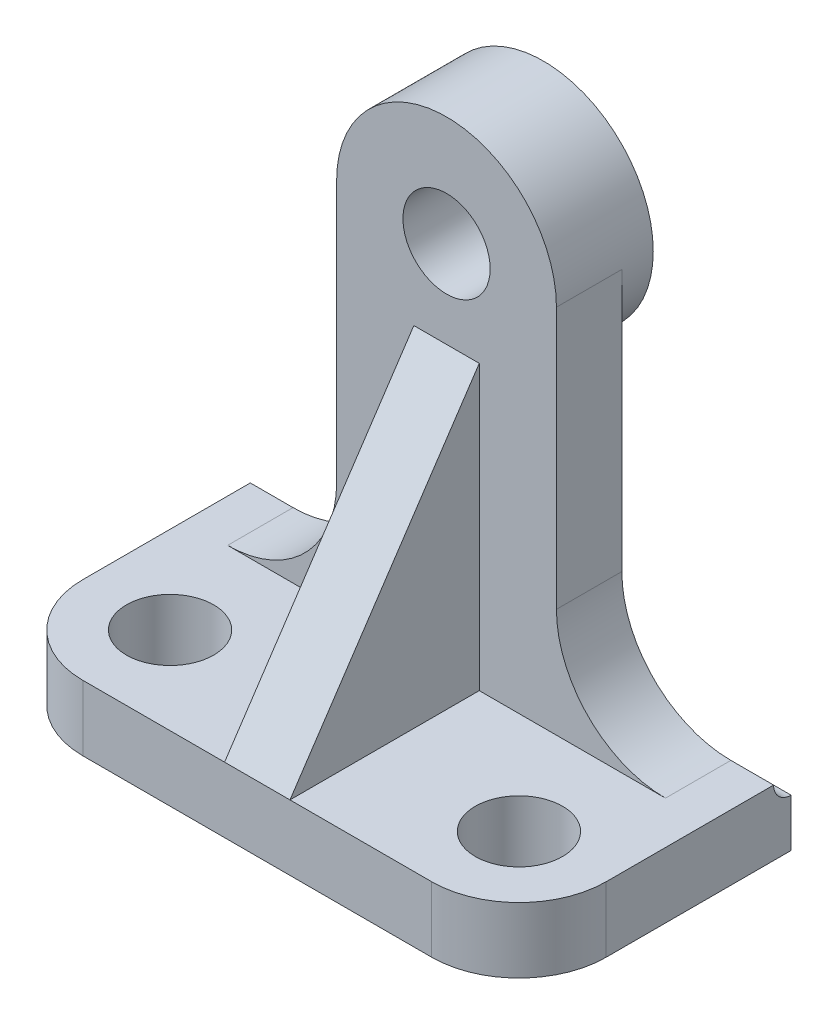
SolidWorks part; units mm, degrees
material "Gray Cast Iron"
ref_plane "Front Plane" through (0, 0, 0) normal (0, 0, 1) x (1, 0, 0)
ref_plane "Top Plane" through (0, 0, 0) normal (0, 1, 0) x (1, 0, 0)
ref_plane "Right Plane" through (0, 0, 0) normal (1, 0, 0) x (0, 0, -1)
ref_axis "X-axis" through (-88.99, 0, 0) along (1, 0, 0)
ref_axis "Y-axis" through (0, 55, 0) along (0, -1, 0)
ref_axis "Z-axis" through (0, 0, -88.99) along (0, 0, 1)
sketch "Sketch1" plane through (0, 0, 0) normal (1, 0, 0) x (0, 0, -1)
  line L0 (0, 0) -> (-37.084, 0)
  line L1 (-37.084, 0) -> (-37.084, -9.525)
  line L2 (-37.084, -9.525) -> (2.54, -9.525)
  line L3 (2.54, -9.525) -> (2.54, -2.54)
  arc A0 (2.54, -2.54) -> (0, 0) centre (2.54, 0) cw
  dimension "D3" = 2.54
  dimension "D1" = 39.624
  dimension "D2" = 9.525
  dimension "D4" = 6.985
extrude "Boss-Extrude1" add sketch "Sketch1" along normal mid plane 76.2
sketch "Sketch2" plane through (0, 0, 0) normal (0, 0, 1) x (1, 0, 0)
  line L0 (-16.002, 0) -> (16.002, 0)
  line L1 (38.1, 0) -> (-38.1, 0) construction
  line L2 (-16.002, 0) -> (-16.002, 53.975)
  line L3 (16.002, 53.975) -> (16.002, 0)
  line L4 (38.1, -9.525) -> (-38.1, -9.525) construction
  arc A0 (-16.002, 53.975) -> (16.002, 53.975) centre (0, 53.975) cw
  dimension "D1" = 16.002
  dimension "D2" = 63.5
extrude "Boss-Extrude2" add sketch "Sketch2" along normal blind 9.525
sketch "Sketch3" plane through (0, 0, 0) normal (0, 0, -1) x (-1, 0, 0)
  circle A0 centre (0, 53.975) radius 16.002
extrude "Boss-Extrude3" add sketch "Sketch3" along normal blind 4.572
sketch "Sketch4" plane through (0, 0, 0) normal (1, 0, 0) x (0, 0, -1)
  line L0 (-9.525, 41.275) -> (-37.084, 0)
  line L1 (-9.525, 0) -> (-9.525, 53.975) construction
  line L2 (-37.084, 0) -> (-9.525, 0)
  line L3 (-9.525, 0) -> (-9.525, 41.275)
  line L4 (-37.084, -9.525) -> (2.54, -9.525) construction
  dimension "D1" = 50.8
extrude "Boss-Extrude4" add sketch "Sketch4" along normal mid plane 9.525
fillet "Fillet1" radius 15.875 2 edges at (-16.002, 0, 4.7625) (16.002, 0, 4.7625)
fillet "Fillet2" radius 12.7 2 edges at (-38.1, -4.7625, 37.084) (38.1, -4.7625, 37.084)
hole_wizard "1/4 (0.5) Diameter Hole1" positions "Sketch6" profile "Sketch7" hole size "1/4" standard "ANSI Inch" end condition through all
sketch "Sketch6" plane through (0, 0, 0) normal (0, 1, 0) x (1, 0, 0)
  point P0 (-25.4, -24.384)
  point P3 (25.4, -24.384)
sketch "Sketch7" plane through (-25.4, 0, 24.384) normal (1, 0, 0) x (0, 0, 1)
  line L0 (0, 0) -> (0, 9.525)
  line L1 (0, 9.525) -> (6.35, 9.525)
  line L2 (6.35, 9.525) -> (6.35, 0)
  line L5 (6.35, 0) -> (0, 0)
  line L11 (0, -6.35) -> (0, 107.95) construction
  dimension "Thru Hole Dia." = 12.7
  dimension "Thru Hole Depth" = 9.525
hole_wizard "1/4 (0.5) Diameter Hole2" positions "Sketch8" profile "Sketch9" hole size "1/4" standard "ANSI Inch" end condition through all
sketch "Sketch8" plane through (0, 0, 9.525) normal (0, 0, 1) x (1, 0, 0)
  point P0 (0, 53.975)
sketch "Sketch9" plane through (0, 53.975, 9.525) normal (1, 0, 0) x (0, -1, 0)
  line L0 (0, 0) -> (0, 14.097)
  line L1 (0, 14.097) -> (6.35, 14.097)
  line L2 (6.35, 14.097) -> (6.35, 0)
  line L5 (6.35, 0) -> (0, 0)
  line L11 (0, -6.35) -> (0, 107.95) construction
  dimension "Thru Hole Dia." = 12.7
  dimension "Thru Hole Depth" = 14.097
